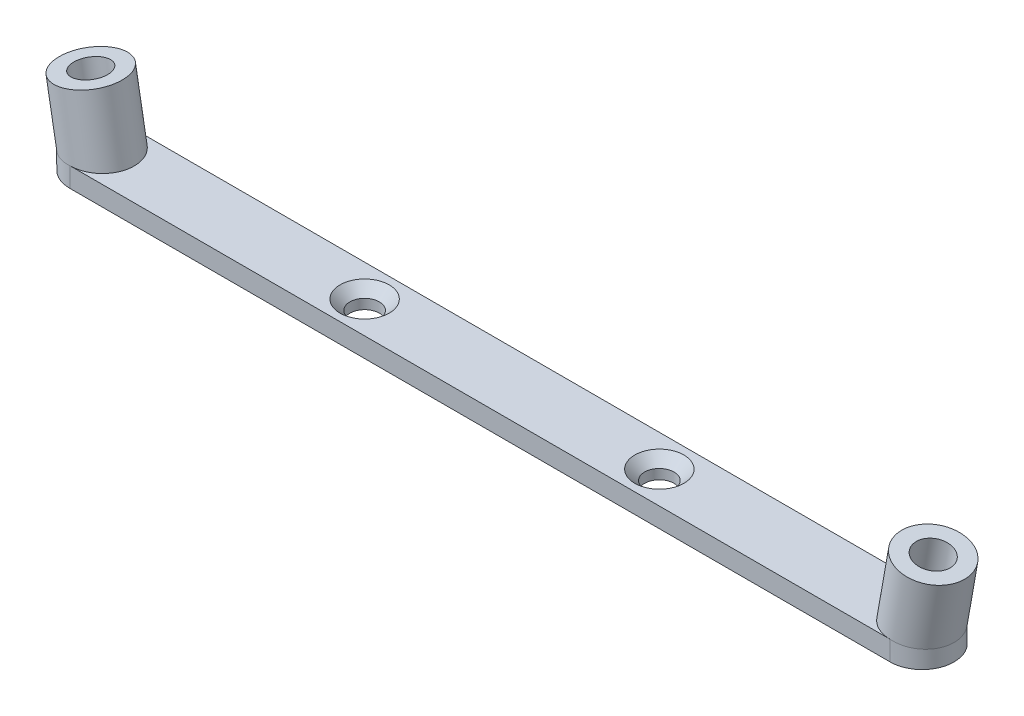
SolidWorks part; units mm, degrees
note: '?' marks a value the reader was unsure of.
ref_plane "Front Plane" through (0, 0, 0) normal (0, 0, 1) x (1, 0, 0)
ref_plane "Top Plane" through (0, 0, 0) normal (0, 1, 0) x (1, 0, 0)
ref_plane "Right Plane" through (0, 0, 0) normal (1, 0, 0) x (0, 0, -1)
ref_plane "TOP SURF" through (0, 2, 0) normal (0, 1, 0) x (1, 0, 0)
sketch "Sketch1" plane through (0, 0, 0) normal (0, 1, 0) x (1, 0, 0)
  line L0 (-45, 0) -> (45, 0) construction
  line L1 (-41.75, 0) -> (41.75, 0) construction
  line L2 (-41.75, 3.25) -> (41.75, 3.25)
  line L3 (-41.75, -3.25) -> (41.75, -3.25)
  arc A2 (-41.75, 3.25) -> (-41.75, -3.25) centre (-41.75, 0) ccw
  arc A3 (41.75, -3.25) -> (41.75, 3.25) centre (41.75, 0) ccw
  point P5 (0, 0)
  dimension "D1" = 90
  dimension "D2" = 45
  dimension "D3" = 6.5
extrude "Boss-Extrude1" add sketch "Sketch1" along normal up to surface (2 mm away) up to plane "TOP SURF"
ref_axis "Axis1" through (-41.75, 2, 3.25) along (0, 0, -1)?
ref_axis "Axis2" through (41.75, 2, 3.25) along (0, 0, -1)?
ref_axis "Axis3" through (45.0466, 2, 0) along (-1, 0, 0)?
ref_plane "STRUT1" through (-1.6009, 9.0794, 0) normal (-0.1736, 0.9848, 0) x (0, 0, -1)
ref_plane "STRUT1 END" through (-2.7296, 15.4806, 0) normal (-0.1736, 0.9848, 0) x (0, 0, -1)
ref_plane "STRUT2" through (1.6009, 9.0794, 0) normal (0.1736, 0.9848, 0) x (0, 0, -1)
ref_plane "STRUT2 END" through (2.7296, 15.4806, 0) normal (0.1736, 0.9848, 0) x (0, 0, -1)
sketch "Sketch2" plane through (-1.6009, 9.0794, 0) normal (-0.1736, 0.9848, 0) x (0, 0, -1)
  line L0 (-3.25, 40.7684) -> (3.25, 40.7684) construction
  line L1 (0, -44.7096) -> (0, 53.7712) construction
  circle A0 centre (0, 40.7684) radius 1.75
  circle A1 centre (0, 40.7684) radius 3.25
  point P0 (0, 40.7684)
  dimension "D2" = 3.5
  dimension "D1" = 1.5
extrude "Boss-Extrude2" add sketch "Sketch2" along normal up to surface and the other way up to surface
sketch "Sketch3" plane through (1.6009, 9.0794, 0) normal (0.1736, 0.9848, 0) x (0, 0, -1)
  line L0 (-3.25, -40.7684) -> (3.25, -40.7684) construction
  line L1 (0, -44.015) -> (0, 54.4658) construction
  circle A0 centre (0, -40.7684) radius 1.75
  circle A1 centre (0, -40.7684) radius 3.25
  point P0 (0, -40.7684)
  dimension "D2" = 3.5
  dimension "D1" = 1.5
extrude "Boss-Extrude3" add sketch "Sketch3" along normal up to surface and the other way up to surface
sketch "Sketch4" plane through (0, 2, 0) normal (0, 1, 0) x (1, 0, 0)
  line L0 (-15, 0) -> (15, 0) construction
  line L1 (45.0466, 0) -> (-54.9534, 0) construction
  circle A0 centre (-15, 0) radius 1.5
  circle A1 centre (15, 0) radius 1.5
  point P6 (0, 0)
  dimension "D1" = 30
extrude "Cut-Extrude1" cut sketch "Sketch4" against normal up to surface (2 mm away) up to face at (0, 0, 0)
chamfer "Chamfer1" distance 1 angle 45 2 edges at (15, 2, 1.5) (-15, 2, 1.5)
equation "\"WIDTH\"= 90"
equation "\"WALLTHICK\"= 1.5"
equation "\"RODDIA\"= 3.5"
equation "\"D1@Sketch1\"=\"WIDTH\""
equation "\"D2@Sketch1\"=\"WIDTH\"/2"
equation "\"D3@Sketch1\"=\"WALLTHICK\"*2 + \"RODDIA\""
equation "\"D1\"= 2"
equation "\"ANGLE\"= 30"
equation "\"D1@Sketch2\"=\"WALLTHICK\""
equation "\"D2@Sketch2\"=\"RODDIA\""
equation "\"D1@Sketch3\"=\"WALLTHICK\""
equation "\"D2@Sketch3\"=\"RODDIA\""
equation "\"SCREWSIZE\"= 3"
equation "\"D2@Sketch4\"=\"SCREWSIZE\""
